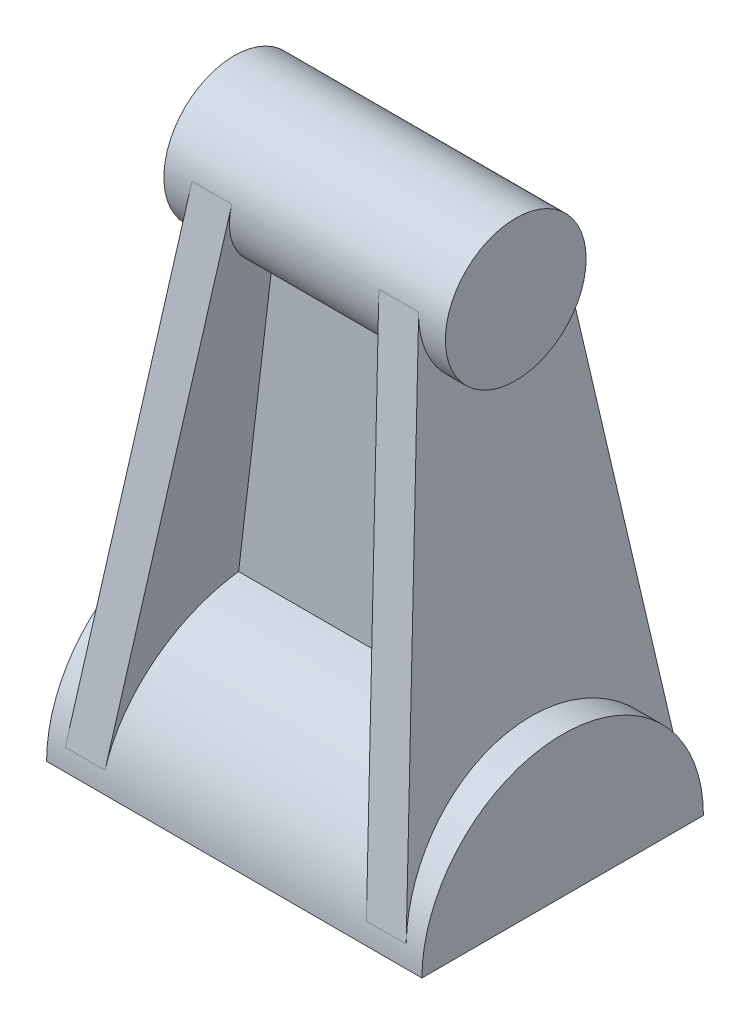
SolidWorks part; units mm, degrees
ref_plane "Front Plane" through (0, 0, 0) normal (0, 0, 1) x (1, 0, 0)
ref_plane "Top Plane" through (0, 0, 0) normal (0, 1, 0) x (1, 0, 0)
ref_plane "Right Plane" through (0, 0, 0) normal (1, 0, 0) x (0, 0, -1)
sketch "Sketch1" plane through (0, 0, 0) normal (1, 0, 0) x (0, 0, -1)
  line L0 (-28.5, 0) -> (28.5, 0)
  line L1 (0, 0) -> (0, 41.7681) construction
  arc A0 (28.5, 0) -> (-28.5, 0) centre (0, 0) ccw
  circle A1 centre (0, 100) radius 14.25
  point P7 (0, 0)
  dimension "D1" = 28.5
  dimension "D2" = 28.5
  dimension "D3" = 100
extrude "Boss-Extrude1" add sketch "Sketch1" along normal mid plane 57 contours L1 A1 | A1 L1 region at (0, 100, 0)
extrude "Boss-Extrude2" add sketch "Sketch1<3>" along normal mid plane 76 separate body contours L0 L1 A0 | L1 L0 A0 region at (0, 12.0958, 12.0958) region at (0, 12.0958, -12.0958)
sketch "Sketch1<3>" plane through (0, 0, 0) normal (1, 0, 0) x (0, 0, -1) same geometry as "Sketch1"
sketch "Sketch2" plane through (0, 0, 0) normal (0, 0, 1) x (1, 0, 0)
  line L0 (13.4443, 114.25) -> (21.5, 114.25)
  line L1 (28.5, 114.25) -> (-28.5, 114.25) construction
  line L2 (21.5, 114.25) -> (35, 0)
  line L3 (38, 0) -> (-38, 0) construction
  line L4 (35, 0) -> (26.9443, 0)
  line L5 (26.9443, 0) -> (13.4443, 114.25)
  line L6 (0, -200000) -> (0, 200041.7681) construction
  dimension "D1" = 21.5
  dimension "D2" = 8
  dimension "D3" = 35
extrude "Boss-Extrude3" add sketch "Sketch2" along normal through all and the other way through all separate body
sketch "Sketch3" plane through (0, 0, 0) normal (1, 0, 0) x (0, 0, -1)
  line L0 (14.1046, 102.0306) -> (-14.1046, 102.0306)
  line L1 (-14.1046, 102.0306) -> (-28.2092, 4.0613)
  line L2 (-28.2092, 4.0613) -> (28.2092, 4.0613)
  line L3 (28.2092, 4.0613) -> (14.1046, 102.0306)
  circle A0 centre (0, 100) radius 14.25 construction
  arc A1 (28.5, 0) -> (-28.5, 0) centre (0, 0) ccw construction
  point P4 (0, 0)
  point P10 (0, 0)
  point P12 (28.5, 4.1036)
  point P13 (0, 0)
extrude "Cut-Extrude1" cut sketch "Sketch3" along normal through all flip side to cut
mirror "Mirror1" about plane through (0, 0, 0) normal (1, 0, 0) of bodies 105
sketch "Sketch4" plane through (0, 0, 0) normal (0, 0, 1) x (1, 0, 0)
  line L0 (-14.8882, 102.0306) -> (14.8882, 102.0306)
  line L1 (14.8882, 102.0306) -> (26.4645, 4.0613)
  line L2 (26.4645, 4.0613) -> (-26.4645, 4.0613)
  line L3 (-26.4645, 4.0613) -> (-14.8882, 102.0306)
extrude "Boss-Extrude5" add sketch "Sketch4" along normal mid plane 8
